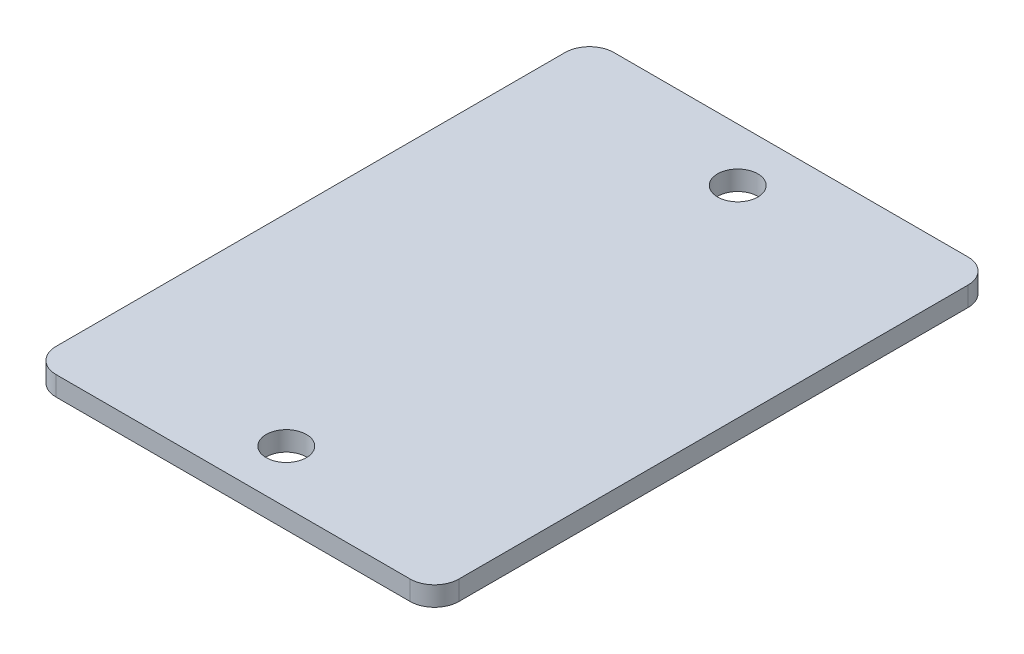
SolidWorks part; units mm, degrees
ref_plane "Front Plane" through (0, 0, 0) normal (0, 0, 1) x (1, 0, 0)
ref_plane "Top Plane" through (0, 0, 0) normal (0, 1, 0) x (1, 0, 0)
ref_plane "Right Plane" through (0, 0, 0) normal (1, 0, 0) x (0, 0, -1)
sketch "Sketch1" plane through (0, 0, 0) normal (0, 1, 0) x (1, 0, 0)
  line L0 (-375.6911, 0) -> (18408.8634, 0) construction
  line L1 (0, -375.6911) -> (0, 18408.8634) construction
  line L3 (-16.51, 22.86) -> (16.51, 22.86)
  line L4 (-16.51, 22.86) -> (-16.51, -22.86)
  line L5 (-16.51, -22.86) -> (16.51, -22.86)
  line L6 (16.51, 22.86) -> (16.51, -22.86)
  line L7 (-16.51, 22.86) -> (16.51, -22.86) construction
  line L8 (-16.51, -22.86) -> (16.51, 22.86) construction
  circle A0 centre (0, 18.5) radius 1.65
  circle A1 centre (0, -18.5) radius 1.65
  point P4 (0, 0)
  dimension "D4" = 3.3
  dimension "D1" = 33.02
  dimension "D2" = 45.72
  dimension "D3" = 37
extrude "Boss-Extrude1" add sketch "Sketch1" along normal blind 1.6
fillet "Fillet1" radius 2 4 edges at (-16.51, 0.8, 22.86) (16.51, 0.8, 22.86) (16.51, 0.8, -22.86) (-16.51, 0.8, -22.86)
equation "\"Frame_Size\" = 220"
equation "\"Frame_Thickness\" = 6"
equation "\"Arm_Width\" = 30"
equation "\"Motor_Mount_Hole_Diameter\" = 8"
equation "\"Motor_Shaft_Diameter\" = 3"
equation "\"Screw_Nut_Diameter\" = 6.5"
equation "\"Screw_Diameter\" = 3"
equation "\"Screw_Shaft_Length\" = 8"
equation "\"Screw_Hole_Separation_C2C\" = 20"
equation "\"Solder_Board_Small_Screw_Hole_Separation\" = 37"
equation "\"Solder_Board_Small_Length\" = 45.72"
equation "\"Solder_Board_Small_Width\" = 33.02"
equation "\"Solder_Board_Small_Thickness\" = 1.6"
equation "\"D1@Sketch1\"=\"Solder_Board_Small_Width\""
equation "\"D2@Sketch1\"=\"Solder_Board_Small_Length\""
equation "\"D3@Sketch1\"=\"Solder_Board_Small_Screw_Hole_Separation\""
equation "\"Solder_Board_Small_Screw_Hole_Diameter\" = 3.3"
equation "\"D4@Sketch1\"=\"Solder_Board_Small_Screw_Hole_Diameter\""
equation "\"D1@Boss-Extrude1\"=\"Solder_Board_Small_Thickness\""
